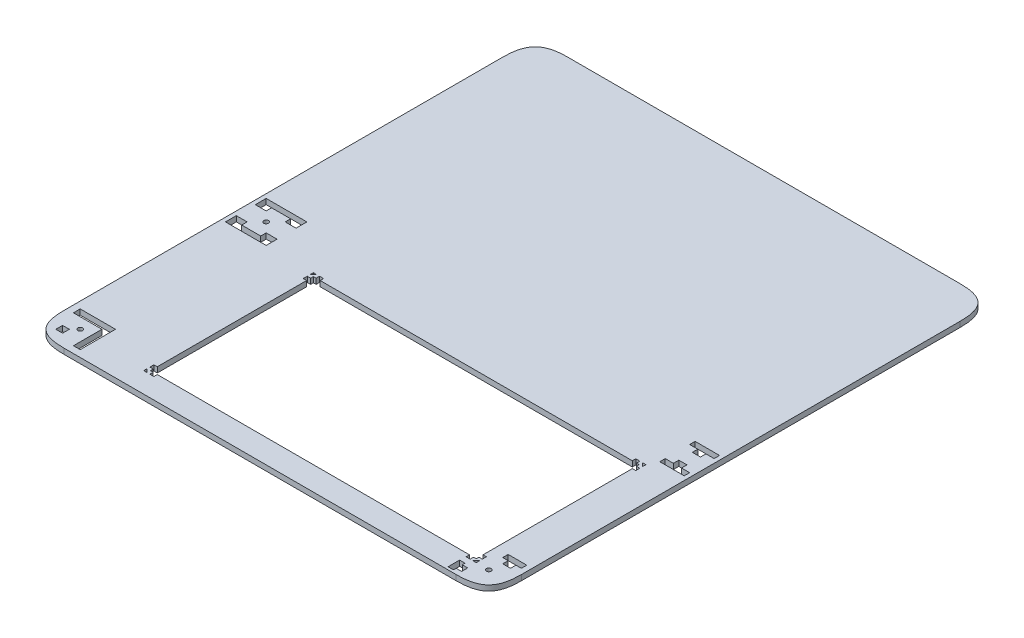
SolidWorks part; units mm, degrees
ref_plane "Front Plane" through (0, 0, 0) normal (0, 0, 1) x (1, 0, 0)
ref_plane "Top Plane" through (0, 0, 0) normal (0, 1, 0) x (1, 0, 0)
ref_plane "Right Plane" through (0, 0, 0) normal (1, 0, 0) x (0, 0, -1)
sketch "Sketch1" plane through (0, 0, 0) normal (0, 1, 0) x (1, 0, 0)
  line L1 (0, 0) -> (337, 0)
  line L2 (0, 0) -> (0, 371.22)
  line L3 (0, 371.22) -> (337, 371.22)
  line L4 (337, 0) -> (337, 371.22)
  line L5 (70.28, 137.5) -> (310.28, 137.5)
  line L6 (70.28, 137.5) -> (70.28, 17.5)
  line L7 (70.28, 17.5) -> (310.28, 17.5)
  line L8 (310.28, 137.5) -> (310.28, 17.5)
  dimension "D1" = 337
  dimension "D2" = 371.22
  dimension "D3" = 240
  dimension "D4" = 120
  dimension "D5" = 17.5
  dimension "D6" = 26.72
extrude "Boss-Extrude1" add sketch "Sketch1" against normal blind 4
fillet "Fillet1" radius 24 4 edges at (0, -2, 0) (337, -2, 0) (0, -2, -371.22) (337, -2, -371.22) conic rho 0.55
sketch "Sketch3" plane through (0, 0, 0) normal (0, 1, 0) x (1, 0, 0)
  line L0 (337, 24) -> (337, 347.22) construction
  line L1 (24, 0) -> (313, 0) construction
  line L2 (0, 347.22) -> (0, 24) construction
  line L3 (309, 4) -> (309, 2)
  line L4 (305, 10.5) -> (309, 10.5)
  line L5 (305, 10.5) -> (305, 2)
  line L6 (305, 2) -> (309, 2)
  line L7 (309, 10.5) -> (309, 8.5)
  line L8 (309, 8.5) -> (313, 8.5)
  line L10 (309, 4) -> (313, 4)
  line L11 (313, 8.5) -> (313, 4)
  line L12 (329, 28) -> (333, 28)
  line L13 (319.28, 32) -> (333, 32)
  line L14 (319.28, 32) -> (319.28, 28)
  line L15 (319.28, 28) -> (323.28, 28)
  line L16 (333, 32) -> (333, 28)
  line L18 (323.28, 28) -> (323.28, 24)
  line L19 (323.28, 24) -> (329, 24)
  line L20 (329, 28) -> (329, 24)
  line L21 (328, 151) -> (334, 151)
  line L30 (26, 5) -> (31, 5)
  line L36 (26, 5) -> (26, 26)
  line L37 (9, 14) -> (14, 14)
  line L38 (9, 14) -> (9, 9)
  line L39 (9, 9) -> (14, 9)
  line L40 (14, 14) -> (14, 9)
  line L41 (26, 31) -> (31, 31)
  line L42 (31, 5) -> (31, 31)
  line L43 (26, 31) -> (5, 31)
  line L45 (26, 26) -> (5, 26)
  line L46 (5, 31) -> (5, 26)
  line L47 (3, 140) -> (33, 140)
  line L48 (3, 140) -> (3, 144)
  line L49 (11, 144) -> (25, 144)
  line L50 (33, 140) -> (33, 144)
  line L52 (3, 144) -> (3, 148)
  line L53 (3, 148) -> (11, 148)
  line L54 (11, 144) -> (11, 148)
  line L56 (33, 144) -> (33, 148)
  line L57 (33, 148) -> (25, 148)
  line L58 (25, 144) -> (25, 148)
  line L59 (3, 170) -> (33, 170)
  line L60 (3, 170) -> (3, 166)
  line L61 (11, 166) -> (25, 166)
  line L62 (33, 170) -> (33, 166)
  line L64 (3, 166) -> (3, 162)
  line L65 (3, 162) -> (11, 162)
  line L66 (11, 166) -> (11, 162)
  line L68 (33, 166) -> (33, 162)
  line L69 (33, 162) -> (25, 162)
  line L70 (25, 166) -> (25, 162)
  line L71 (316, 147) -> (334, 147)
  line L72 (316, 147) -> (316, 151)
  line L73 (316, 151) -> (322, 151)
  line L74 (334, 147) -> (334, 151)
  line L76 (322, 151) -> (322, 155)
  line L77 (322, 155) -> (328, 155)
  line L78 (328, 151) -> (328, 155)
  line L79 (328, 169) -> (334, 169)
  line L80 (316, 173) -> (334, 173)
  line L81 (316, 173) -> (316, 169)
  line L82 (316, 169) -> (322, 169)
  line L83 (334, 173) -> (334, 169)
  line L85 (322, 169) -> (322, 165)
  line L86 (322, 165) -> (328, 165)
  line L87 (328, 169) -> (328, 165)
  circle A0 centre (322, 15) radius 1.75
  circle A1 centre (18, 18) radius 1.75
  circle A2 centre (18, 155) radius 1.75
  point P37 (5, 28.5)
  dimension "D3" = 3.5
  dimension "D6" = 3.5
  dimension "D45" = 3.5
  dimension "D1" = 15
  dimension "D2" = 15
  dimension "D4" = 18
  dimension "D5" = 18
  dimension "D7" = 24
  dimension "D8" = 4
  dimension "D9" = 2
  dimension "D10" = 2
  dimension "D11" = 4.5
  dimension "D12" = 2
  dimension "D13" = 4
  dimension "D14" = 4
  dimension "D15" = 13.72
  dimension "D16" = 4
  dimension "D17" = 4
  dimension "D18" = 4
  dimension "D19" = 4
  dimension "D20" = 24
  dimension "D21" = 5
  dimension "D22" = 5
  dimension "D23" = 9
  dimension "D24" = 9
  dimension "D25" = 26
  dimension "D26" = 5
  dimension "D27" = 5
  dimension "D28" = 5
  dimension "D29" = 21
  dimension "D30" = 5
  dimension "D31" = 30
  dimension "D32" = 4
  dimension "D33" = 4
  dimension "D34" = 8
  dimension "D35" = 8
  dimension "D36" = 4
  dimension "D37" = 30
  dimension "D38" = 4
  dimension "D39" = 4
  dimension "D40" = 4
  dimension "D41" = 30
  dimension "D42" = 140
  dimension "D43" = 3
  dimension "D44" = 3
  dimension "D46" = 11
  dimension "D47" = 4
  dimension "D48" = 4
  dimension "D49" = 4
  dimension "D50" = 18
  dimension "D51" = 3
  dimension "D52" = 6
  dimension "D53" = 6
  dimension "D54" = 4
  dimension "D55" = 4
  dimension "D56" = 4
  dimension "D57" = 18
  dimension "D58" = 6
  dimension "D59" = 6
  dimension "D60" = 10
  dimension "D61" = 147
extrude "Cut-Extrude1" cut sketch "Sketch3" against normal up to next
ref_plane "Plane3" through (190.28, 0, 0) normal (-1, 0, 0) x (0, 0, 1)
ref_plane "Plane6" through (0, 0, -77.5) normal (0, 0, 1) x (1, 0, 0)
sketch "Sketch5" plane through (0, 0, 0) normal (0, 1, 0) x (1, 0, 0)
  line L0 (310.28, 17.5) -> (310.28, 137.5) construction
  line L3 (310.28, 15) -> (312.78, 15)
  line L4 (312.78, 17.5) -> (312.78, 15)
  line L5 (310.28, 22.5) -> (312.78, 22.5)
  line L6 (310.28, 22.5) -> (310.28, 19.5)
  line L7 (310.28, 19.5) -> (312.78, 19.5)
  line L8 (312.78, 22.5) -> (312.78, 19.5)
  line L9 (70.28, 17.5) -> (310.28, 17.5) construction
  line L10 (305.28, 17.5) -> (308.28, 17.5)
  line L11 (305.28, 17.5) -> (305.28, 15)
  line L12 (305.28, 15) -> (308.28, 15)
  line L13 (308.28, 17.5) -> (308.28, 15)
  line L14 (310.28, 15) -> (312.78, 17.5)
  dimension "D1" = 2.5
  dimension "D2" = 2.5
  dimension "D4" = 3
  dimension "D6" = 3
extrude "Cut-Extrude2" cut sketch "Sketch5" against normal up to next
mirror "Mirror1" about plane through (0, 0, -77.5) normal (0, 0, 1) of "Cut-Extrude2" second plane through (190.28, 0, 0) second plane normal (-1, 0, 0)
